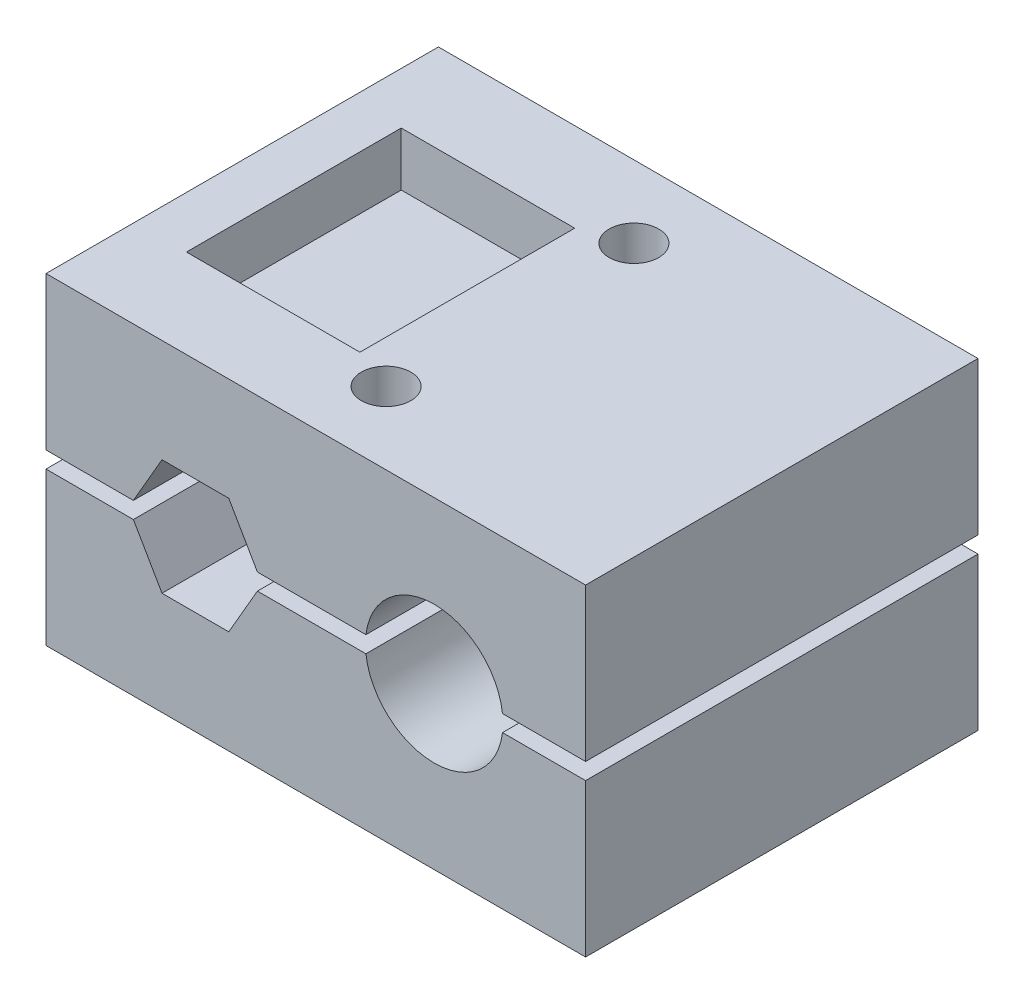
SolidWorks part; units mm, degrees
ref_plane "Front Plane" through (0, 0, 0) normal (0, 0, 1) x (1, 0, 0)
ref_plane "Top Plane" through (0, 0, 0) normal (0, 1, 0) x (1, 0, 0)
ref_plane "Right Plane" through (0, 0, 0) normal (1, 0, 0) x (0, 0, -1)
sketch "Sketch2" plane through (0, 0, 0) normal (0, 0, 1) x (1, 0, 0)
  line L0 (0, 0) -> (0, 0.0003) construction
  line L1 (-11.3872, 0.0003) -> (-9.3342, -3.5557)
  line L2 (-9.3342, -3.5557) -> (-5.2281, -3.5557)
  line L3 (-5.2281, -3.5557) -> (-3.175, 0.0003)
  line L4 (-3.175, 0.0003) -> (-5.2281, 3.5563)
  line L5 (-5.2281, 3.5563) -> (-9.3342, 3.5563)
  line L6 (-9.3342, 3.5563) -> (-11.3872, 0.0003)
  line L9 (-3.175, 0.0003) -> (3.175, 0.0003) construction
  line L11 (-16.4672, 9.9063) -> (16.7132, 9.9063)
  line L12 (-16.4672, 9.9063) -> (-16.4672, -9.9057)
  line L13 (-16.4672, -9.9057) -> (16.7132, -9.9057)
  line L14 (16.7132, 9.9063) -> (16.7132, -9.9057)
  line L16 (-11.3872, 0.0003) -> (-16.4672, 0.0003) construction
  circle A0 centre (-7.2811, 0.0003) radius 3.556 construction
  circle A1 centre (7.4041, 0.0003) radius 4.2291
  point P10 (3.175, 0.0003)
  point P13 (11.6332, 0.0003)
  point P25 (0, -15.0238)
  dimension "D2" = 8.4582
  dimension "D1" = 7.112
  dimension "D3" = 6.35
  dimension "D4" = 0.0003
  dimension "D5" = 5.08
  dimension "D6" = 6.35
  dimension "D7" = 6.35
  dimension "D8" = 5.08
  dimension "D9" = 33.1804
  dimension "D10" = 4.1061
extrude "Boss-Extrude3" add sketch "Sketch2" along normal mid plane 24.13
sketch "Sketch7" plane through (0, 0, 0) normal (0, 1, 0) x (1, 0, 0)
  line L0 (-16.4672, -12.065) -> (-16.4672, 12.065) construction
  line L2 (-13.2922, -6.604) -> (-2.6242, -6.604)
  line L3 (-13.2922, -6.604) -> (-13.2922, 6.604)
  line L4 (-13.2922, 6.604) -> (-2.6242, 6.604)
  line L5 (-2.6242, -6.604) -> (-2.6242, 6.604)
  line L6 (-13.2922, -6.604) -> (-2.6242, 6.604) construction
  line L8 (0, 0) -> (0, 7.62) construction
  line L10 (0, -7.62) -> (0, 0) construction
  line L12 (-13.2922, 6.604) -> (-2.6242, -6.604) construction
  circle A0 centre (0, -7.62) radius 1.524
  circle A1 centre (0, 7.62) radius 1.524
  point P5 (-7.9582, 0)
  point P10 (0, 9.144)
  point P11 (0, -9.144)
  dimension "D1" = 3.048
  dimension "D2" = 13.208
  dimension "D3" = 10.668
  dimension "D4" = 7.62
  dimension "D5" = 3.175
extrude "Cut-Extrude5" cut sketch "Sketch7" against normal through all and the other way through all contours A1 | A0
extrude "Cut-Extrude7" cut sketch "Sketch7<6>" against normal blind 3.302 from surface contours L2 L5 L4 L3 region at (-7.9582, 0, 0) starting at face at (0, 9.9063, 9.144)
sketch "Sketch7<6>" plane through (0, 0, 0) normal (0, 1, 0) x (1, 0, 0) same geometry as "Sketch7"
sketch "Sketch8" plane through (0, 0, 0) normal (0, 0, 1) x (1, 0, 0)
  line L1 (-19.05, -0.508) -> (19.05, -0.508)
  line L2 (-19.05, -0.508) -> (-19.05, 0.508)
  line L3 (-19.05, 0.508) -> (19.05, 0.508)
  line L4 (19.05, -0.508) -> (19.05, 0.508)
  line L5 (-19.05, -0.508) -> (19.05, 0.508) construction
  line L6 (-19.05, 0.508) -> (19.05, -0.508) construction
  point P0 (0, 0)
  dimension "D1" = 1.016
  dimension "D2" = 38.1
extrude "Cut-Extrude8" cut sketch "Sketch8" against normal through all and the other way through all
split "Split3" [suppressed] bodies to split 117
